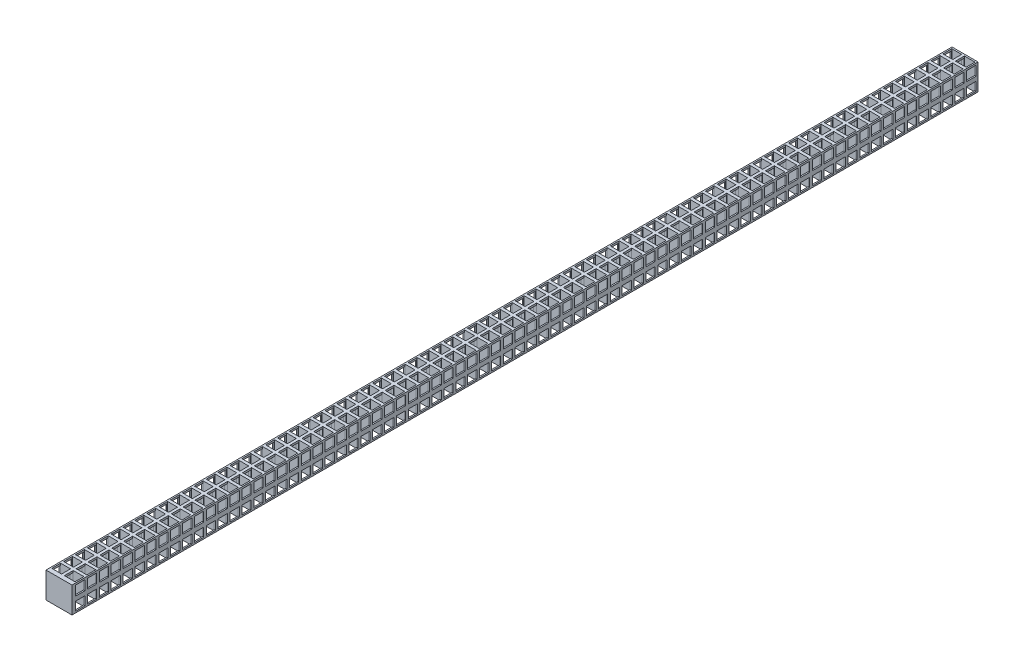
SolidWorks part; units mm, degrees
ref_plane "Alzado" through (0, 0, 0) normal (0, 0, 1) x (1, 0, 0)
ref_plane "Planta" through (0, 0, 0) normal (0, 1, 0) x (1, 0, 0)
ref_plane "Vista lateral" through (0, 0, 0) normal (1, 0, 0) x (0, 0, -1)
sketch "Croquis1" plane through (0, 0, 0) normal (0, 0, 1) x (1, 0, 0)
  line L1 (-175, 175) -> (175, 175)
  line L2 (-175, 175) -> (-175, -175)
  line L3 (-175, -175) -> (175, -175)
  line L4 (175, 175) -> (175, -175)
  line L5 (-175, 175) -> (175, -175) construction
  line L6 (-175, -175) -> (175, 175) construction
  point P0 (0, 0)
  dimension "D1" = 350
  dimension "D2" = 350
extrude "Saliente-Extruir1" add sketch "Croquis1" along normal blind 12200
sketch "Croquis2" plane through (0, 175, 0) normal (0, 1, 0) x (1, 0, 0)
  line L1 (-155.9826, -21.6819) -> (-22.9987, -21.6819)
  line L2 (-155.9826, -21.6819) -> (-155.9826, -141.6282)
  line L3 (-155.9826, -141.6282) -> (-22.9987, -141.6282)
  line L4 (-22.9987, -21.6819) -> (-22.9987, -141.6282)
  line L5 (-155.9826, -21.6819) -> (-22.9987, -141.6282) construction
  line L6 (-155.9826, -141.6282) -> (-22.9987, -21.6819) construction
  line L7 (13.5067, -21.6819) -> (156.9206, -21.6819)
  line L8 (13.5067, -21.6819) -> (13.5067, -141.6282)
  line L9 (13.5067, -141.6282) -> (156.9206, -141.6282)
  line L10 (156.9206, -21.6819) -> (156.9206, -141.6282)
  line L11 (13.5067, -21.6819) -> (156.9206, -141.6282) construction
  line L12 (13.5067, -141.6282) -> (156.9206, -21.6819) construction
  point P0 (-89.4906, -81.6551)
  point P6 (85.2136, -81.6551)
extrude "Cortar-Extruir1" cut sketch "Croquis2" against normal blind 12200
pattern_linear "MatrizL1" count 76 spacing 160 along (0, 0, 1) of "Cortar-Extruir1"
sketch "Croquis3" plane through (175, 0, 0) normal (1, 0, 0) x (0, 0, -1)
  line L1 (-26.6974, 150.2665) -> (-151.6043, 150.2665)
  line L2 (-26.6974, 150.2665) -> (-26.6974, 21.5745)
  line L3 (-26.6974, 21.5745) -> (-151.6043, 21.5745)
  line L4 (-151.6043, 150.2665) -> (-151.6043, 21.5745)
  line L5 (-26.6974, 150.2665) -> (-151.6043, 21.5745) construction
  line L6 (-26.6974, 21.5745) -> (-151.6043, 150.2665) construction
  line L7 (-26.6974, -37.1663) -> (-151.6043, -37.1663)
  line L8 (-26.6974, -37.1663) -> (-26.6974, -154.5031)
  line L9 (-26.6974, -154.5031) -> (-151.6043, -154.5031)
  line L10 (-151.6043, -37.1663) -> (-151.6043, -154.5031)
  line L11 (-26.6974, -37.1663) -> (-151.6043, -154.5031) construction
  line L12 (-26.6974, -154.5031) -> (-151.6043, -37.1663) construction
  point P0 (-89.1509, 85.9205)
  point P5 (-89.1509, -95.8347)
extrude "Cortar-Extruir2" cut sketch "Croquis3" against normal blind 12200
pattern_linear "MatrizL2" count 76 spacing 160 along (0, 0, 1) of "Cortar-Extruir2"
